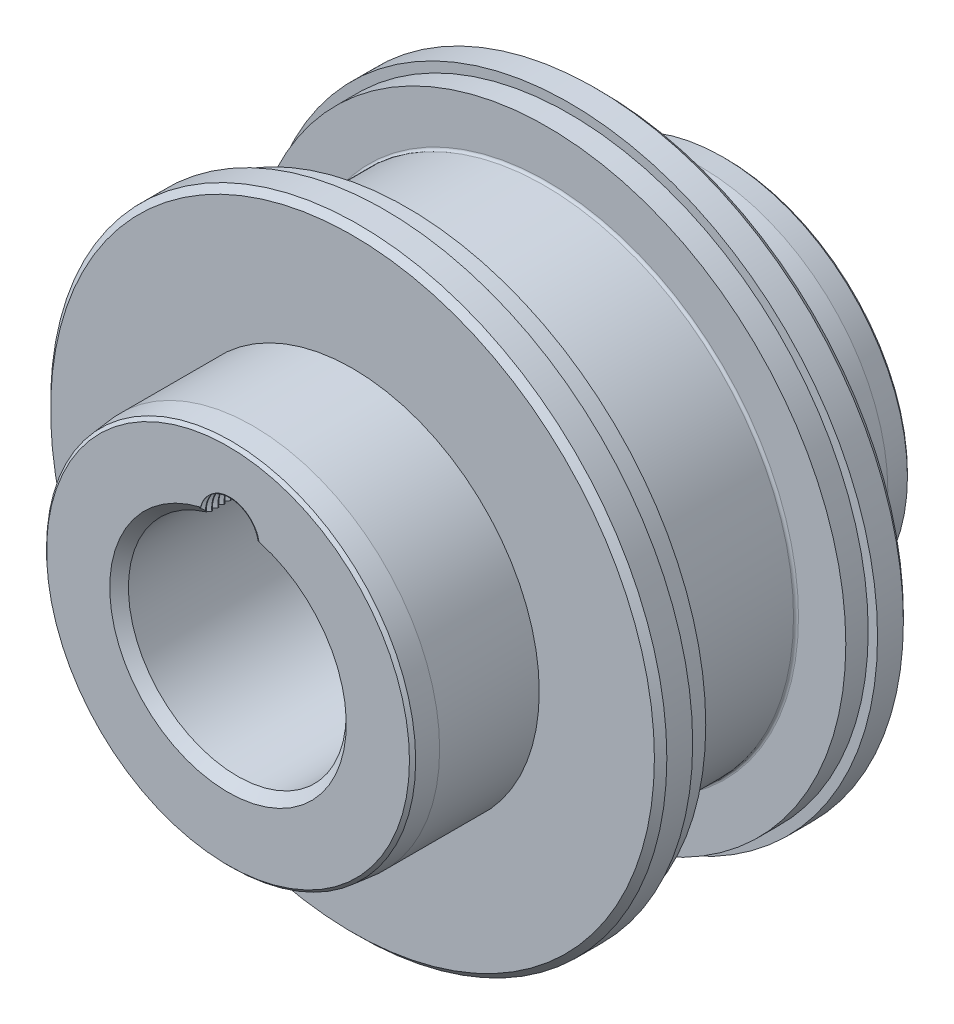
SolidWorks part; units mm, degrees
ref_plane "Front Plane" through (0, 0, 0) normal (0, 0, 1) x (1, 0, 0)
ref_plane "Top Plane" through (0, 0, 0) normal (0, 1, 0) x (1, 0, 0)
ref_plane "Right Plane" through (0, 0, 0) normal (1, 0, 0) x (0, 0, -1)
sketch "Sketch2" plane through (0, 0, 0) normal (1, 0, 0) x (0, 0, -1)
  line L0 (-40, 0) -> (40, 0) construction
  line L1 (0, 0) -> (0, 17.5) construction
  line L2 (40, 17.5) -> (-40, 17.5) construction
  line L3 (-38.5, 17.5) -> (5, 17.5)
  line L4 (6, 18.5) -> (36, 18.5)
  line L5 (40, 19.5) -> (40, 29.15)
  line L6 (40, 29.15) -> (39.5, 29.65)
  line L7 (39.5, 29.65) -> (36, 30)
  line L8 (36, 30) -> (20, 30)
  line L9 (20, 30) -> (20, 48.5)
  line L10 (36, 18.5) -> (40, 19.5)
  line L11 (19, 49.5) -> (14.85, 49.5)
  line L12 (14.85, 49.5) -> (14.85, 48)
  line L13 (14.85, 48) -> (11.25, 48)
  line L14 (11.25, 48) -> (11.25, 40.4)
  line L15 (20, 48.5) -> (19, 49.5)
  line L16 (-20, 30) -> (-20, 48.5)
  line L17 (-20, 48.5) -> (-19, 49.5)
  line L18 (-11.25, 48) -> (-11.25, 40.4)
  line L19 (-14.85, 48) -> (-11.25, 48)
  line L20 (-14.85, 49.5) -> (-14.85, 48)
  line L21 (-19, 49.5) -> (-14.85, 49.5)
  line L22 (-36, 30) -> (-20, 30)
  line L23 (-39.5, 29.65) -> (-36, 30)
  line L24 (-40, 29.15) -> (-39.5, 29.65)
  line L25 (-40, 29.15) -> (-40, 19)
  line L26 (-10.85, 40) -> (10.85, 40)
  line L27 (-40, 19) -> (-38.5, 17.5)
  arc A0 (5, 17.5) -> (6, 18.5) centre (6, 17.5) cw
  arc A1 (11.25, 40.4) -> (10.85, 40) centre (10.85, 40.4) cw
  arc A2 (-11.25, 40.4) -> (-10.85, 40) centre (-10.85, 40.4) ccw
  point P4 (0, 0)
  point P10 (0, 17.5)
  point P15 (40, 18.5)
  point P19 (20, 49.5)
  point P34 (-20, 49.5)
  point P40 (11.25, 40)
  point P43 (-11.25, 40)
  dimension "D4" = 35
  dimension "D18" = 0.4
  dimension "D1" = 80
  dimension "D2" = 17.5
  dimension "D3" = 1
  dimension "D5" = 11.5
  dimension "D6" = 4
  dimension "D7" = 20
  dimension "D8" = 19.5
  dimension "D9" = 135
  dimension "D10" = 0.5
  dimension "D11" = 4
  dimension "D12" = 1
  dimension "D13" = 9.65
  dimension "D14" = 8.75
  dimension "D15" = 8
  dimension "D16" = 3.6
  dimension "D17" = 1.5
revolve "Revolve1" add sketch "Sketch2" angle 360 about L0
sketch "Sketch3" plane through (0, 0, 40) normal (0, 0, 1) x (1, 0, 0)
  circle A0 centre (0, 0) radius 17.5 construction
  point P0 (0, 17.5)
hole_wizard "M10 Clearance Hole1" positions "Sketch3" profile "Sketch4" hole size "M10" standard "ISO"
sketch "Sketch4" plane through (0, 17.5, 40) normal (1, 0, 0) x (0, -1, 0)
  line L0 (0, 0) -> (0, 20.7039)
  line L1 (0, 20.7039) -> (4.5, 18)
  line L2 (4.5, 18) -> (4.5, 0)
  line L5 (4.5, 0) -> (0, 0)
  line L10 (0, 20.7039) -> (-4.5, 18) construction
  line L11 (0, -6.35) -> (0, 107.95) construction
  dimension "Hole Dia." = 9
  dimension "Hole Depth" = 18
  dimension "Drill Angle" = 118
thread "Thread1" pitch 1 start angle 0, offset 1, length 0, pitch 1, diameter 9
ref_plane "Plane1" through (-4.5, 17.5, 41) normal (0, 1, 0) x (1, 0, 0)
sketch "Thread Profile1" plane through (-4.5, 17.5, 41) normal (0, 1, 0) x (1, 0, 0)
  line L0 (0, 0) -> (0, 1) construction
  line L11 (0, 0) -> (0, 0.875)
  line L12 (0, 0.875) -> (-0.5413, 0.5625)
  line L13 (-0.5413, 0.5625) -> (-0.5413, 0.3125)
  line L15 (-0.5413, 0.3125) -> (0, 0)
  line L17 (-0.5413, 0.4375) -> (0, 0.4375) construction
  point P2 (0, 0)
  dimension "Pitch" = 1
  dimension "Profile_Angle" = 60
  dimension "Profile_Land" = 0.25
  dimension "Profile_Height" = 0.5413
